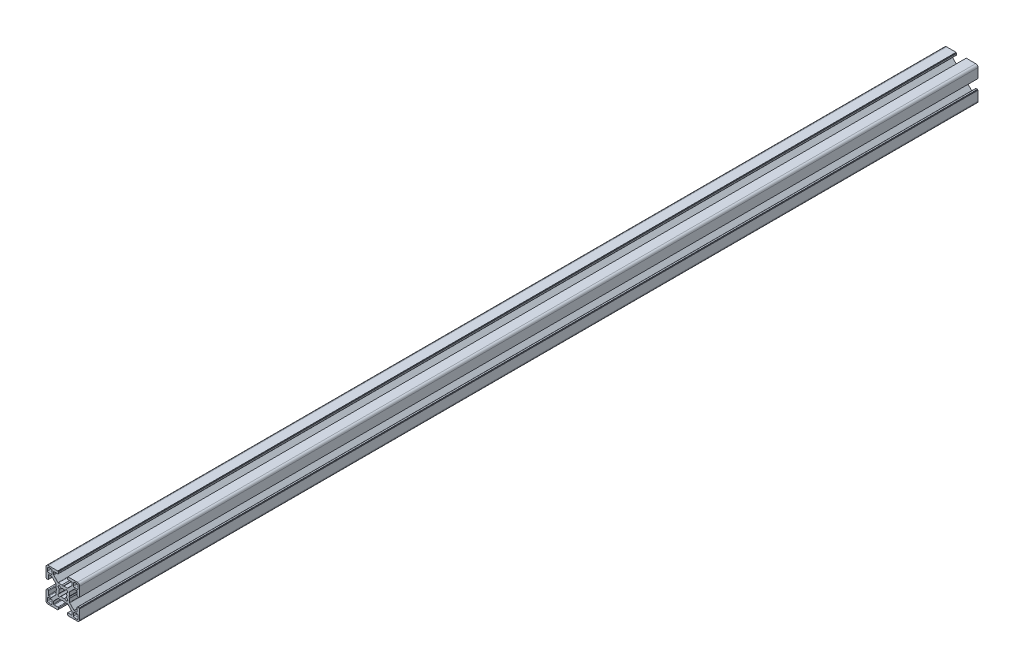
SolidWorks part; units mm, degrees
ref_plane "Front Plane" through (0, 0, 0) normal (0, 0, 1) x (1, 0, 0)
ref_plane "Top Plane" through (0, 0, 0) normal (0, 1, 0) x (1, 0, 0)
ref_plane "Right Plane" through (0, 0, 0) normal (1, 0, 0) x (0, 0, -1)
sketch "Sketch1" plane through (0, 0, 0) normal (0, 0, 1) x (1, 0, 0)
  line L0 (-15, 0) -> (15, 0) construction
  line L1 (0, -15) -> (0, 15) construction
  line L2 (-4.5, 15) -> (4.5, 15) construction
  line L3 (-4, -15) -> (4, -15) construction
  line L4 (-4.5, 15) -> (-4.5, 14.5)
  line L5 (-4.5, 14.5) -> (-4, 14.5)
  line L6 (-4, 14.5) -> (-4, 13.29)
  line L7 (-4.5, 12.79) -> (-7.7675, 12.79)
  line L8 (-8.2675, 12.29) -> (-8.2675, 10.2707)
  line L9 (-8.1211, 9.9171) -> (-4.3504, 6.1464)
  line L10 (-3.9968, 6) -> (0, 6)
  line L11 (0, 0) -> (-15, 15) construction
  line L12 (-4.5, 15) -> (-12.968, 15)
  line L14 (-12.705, 9.5135) -> (-10.5135, 9.5135)
  line L15 (-13.705, 10.5135) -> (-13.705, 12.705)
  line L16 (-12.705, 13.705) -> (-10.5135, 13.705)
  line L17 (-9.5135, 10.5135) -> (-9.5135, 12.705)
  line L18 (-13.705, 9.5135) -> (-9.5135, 13.705) construction
  line L19 (-13.705, 13.705) -> (-9.5135, 9.5135) construction
  line L20 (-3.1568, 4.5038) -> (-1.5303, 3.1477) construction
  line L21 (-4.5038, 3.1568) -> (-3.1477, 1.5303) construction
  line L22 (-6, 3.9968) -> (-6, 0)
  line L23 (-9.9171, 8.1211) -> (-6.1464, 4.3504)
  line L24 (-15, 4.5) -> (-15, 12.968)
  line L25 (-12.29, 8.2675) -> (-10.2707, 8.2675)
  line L26 (-12.79, 4.5) -> (-12.79, 7.7675)
  line L27 (-14.5, 4) -> (-13.29, 4)
  line L28 (-14.5, 4.5) -> (-14.5, 4)
  line L29 (-15, 4.5) -> (-14.5, 4.5)
  circle A0 centre (0, 0) radius 3.5
  arc A1 (-12.968, 15) -> (-15, 12.968) centre (-12.968, 12.968) ccw
  circle A2 centre (0, 0) radius 5.5 construction
  arc A3 (-10.5135, 9.5135) -> (-9.5135, 10.5135) centre (-10.5135, 10.5135) ccw
  arc A4 (-13.705, 12.705) -> (-12.705, 13.705) centre (-12.705, 12.705) cw
  arc A5 (-10.5135, 13.705) -> (-9.5135, 12.705) centre (-10.5135, 12.705) cw
  arc A6 (-12.705, 9.5135) -> (-13.705, 10.5135) centre (-12.705, 10.5135) cw
  arc A7 (-12.79, 4.5) -> (-13.29, 4) centre (-13.29, 4.5) cw
  arc A8 (-12.29, 8.2675) -> (-12.79, 7.7675) centre (-12.29, 7.7675) ccw
  arc A9 (-9.9171, 8.1211) -> (-10.2707, 8.2675) centre (-10.2707, 7.7675) ccw
  arc A10 (-6, 3.9968) -> (-6.1464, 4.3504) centre (-6.5, 3.9968) ccw
  arc A11 (-4.3504, 6.1464) -> (-3.9968, 6) centre (-3.9968, 6.5) ccw
  arc A12 (-4, 13.29) -> (-4.5, 12.79) centre (-4.5, 13.29) cw
  arc A13 (-7.7675, 12.79) -> (-8.2675, 12.29) centre (-7.7675, 12.29) ccw
  arc A14 (-8.2675, 10.2707) -> (-8.1211, 9.9171) centre (-7.7675, 10.2707) ccw
  point P4 (0, 0)
  point P8 (0, 0)
  point P13 (0, 15)
  point P15 (0, -15)
  point P16 (0, 6)
  point P23 (-11.6092, 11.6093)
  point P26 (0, 6)
  point P62 (-12.79, 4)
  point P65 (-12.79, 8.2675)
  point P68 (-10.0636, 8.2675)
  point P71 (-6, 4.2039)
  point P74 (-4.2039, 6)
  point P77 (-4, 12.79)
  point P80 (-8.2675, 12.79)
  point P83 (-8.2675, 10.0636)
  dimension "Center Hole Diameter" = 7
  dimension "D11" = 2.032
  dimension "D9" = 11
  dimension "D13" = 1
  dimension "D14" = 0.5
  dimension "Rail Height" = 30
  dimension "Rail Width" = 30
  dimension "T-Slot Width" = 8
  dimension "T-Slot Depth" = 9
  dimension "D1" = 9
  dimension "D2" = 45
  dimension "D3" = 8
  dimension "D4" = 2.21
  dimension "D5" = 16.535
  dimension "D7" = 2.54
  dimension "D6" = 1.295
  dimension "D8" = 1.246
  dimension "D10" = 10.36
  dimension "D12" = 1.905
sketch "Sketch2" plane through (0, 0, 0) normal (1, 0, 0) x (0, 0, -1)
  line L0 (-76.2, 0) -> (76.2, 0) construction
  line L2 (0, -15) -> (0, 15) construction
  line L3 (0, -15) -> (0, 15) construction
  line L4 (-76.2, -15) -> (-76.2, 15) construction
  line L5 (76.2, -15) -> (76.2, 15) construction
  point P0 (-38.7, 0)
  point P3 (0, 0)
  point P4 (38.7, 0)
  point P12 (-76.2, 0)
  point P14 (76.2, 0)
  dimension "Length" = 152.4
  dimension "D1" = 37.5
sketch "Sketch3" plane through (0, 0, 0) normal (0, 0, 1) x (1, 0, 0)
  line L0 (-4.5038, 3.1568) -> (-3.1477, 1.5303)
  line L1 (0, 3.5) -> (0, 5.5)
  line L2 (-5.5, 0) -> (-3.5, 0)
  line L7 (-6, 3.9968) -> (-6, 0) construction
  line L31 (-9.9171, 8.1211) -> (-6.1464, 4.3504) construction
  line L117 (-12.29, 8.2675) -> (-10.2707, 8.2675) construction
  line L118 (-12.79, 4.5) -> (-12.79, 7.7675) construction
  line L157 (-12.705, 9.5135) -> (-10.5135, 9.5135)
  line L158 (-9.5135, 10.5135) -> (-9.5135, 12.705)
  line L163 (-10.5135, 13.705) -> (-12.705, 13.705)
  line L164 (-13.705, 12.705) -> (-13.705, 10.5135)
  line L165 (-12.705, 9.5135) -> (-10.5135, 9.5135)
  line L166 (-9.5135, 10.5135) -> (-9.5135, 12.705)
  line L167 (-10.5135, 13.705) -> (-12.705, 13.705)
  line L168 (-13.705, 12.705) -> (-13.705, 10.5135)
  line L169 (-14.5, 4) -> (-13.29, 4) construction
  line L170 (-14.5, 4.5) -> (-14.5, 4) construction
  line L171 (-15, 4.5) -> (-14.5, 4.5) construction
  line L172 (-15, 4.5) -> (-15, 12.968) construction
  line L173 (-4.5, 15) -> (-12.968, 15) construction
  line L174 (-4.5, 15) -> (-4.5, 14.5) construction
  line L175 (-4.5, 14.5) -> (-4, 14.5) construction
  line L176 (-4, 14.5) -> (-4, 13.29) construction
  line L177 (-4.5, 12.79) -> (-7.7675, 12.79) construction
  line L178 (-8.2675, 12.29) -> (-8.2675, 10.2707) construction
  line L179 (-8.1211, 9.9171) -> (-4.3504, 6.1464) construction
  line L180 (-3.9968, 6) -> (0, 6) construction
  line L181 (-6, 3.9968) -> (-6, 0.866)
  line L182 (-9.9171, 8.1211) -> (-6.1464, 4.3504)
  line L183 (-12.29, 8.2675) -> (-10.2707, 8.2675)
  line L184 (-12.79, 4.5) -> (-12.79, 7.7675)
  line L185 (-14.5, 4) -> (-13.29, 4)
  line L186 (-14.5, 4.5) -> (-14.5, 4)
  line L187 (-15, 4.5) -> (-14.5, 4.5)
  line L188 (-15, 4.5) -> (-15, 12.968)
  line L189 (-4.5, 15) -> (-12.968, 15)
  line L190 (-4.5, 15) -> (-4.5, 14.5)
  line L191 (-4.5, 14.5) -> (-4, 14.5)
  line L192 (-4, 14.5) -> (-4, 13.29)
  line L193 (-4.5, 12.79) -> (-7.7675, 12.79)
  line L194 (-8.2675, 12.29) -> (-8.2675, 10.2707)
  line L195 (-8.1211, 9.9171) -> (-4.3504, 6.1464)
  line L196 (-3.9968, 6) -> (-0.866, 6)
  line L197 (-0.866, 6) -> (0, 5.5)
  line L198 (0, -15) -> (0, 15) construction
  line L199 (0, 0) -> (-15, 15) construction
  line L200 (0, 0) -> (-15, 15) construction
  line L201 (-3.1568, 4.5038) -> (-1.5303, 3.1477) construction
  line L202 (-3.1568, 4.5038) -> (-1.5303, 3.1477)
  line L203 (-6, 0.866) -> (-5.5, 0)
  line L204 (-15, 0) -> (15, 0) construction
  line L205 (-15, 0) -> (15, 0) construction
  line L206 (0, -15) -> (0, 15) construction
  arc A0 (-3.5, 0) -> (-3.1477, 1.5303) centre (0, 0) cw
  arc A10 (-6, 3.9968) -> (-6.1464, 4.3504) centre (-6.5, 3.9968) ccw construction
  circle A16 centre (0, 0) radius 3.5
  arc A18 (0, 3.5) -> (-1.5303, 3.1477) centre (0, 0) ccw
  arc A20 (-9.9171, 8.1211) -> (-10.2707, 8.2675) centre (-10.2707, 7.7675) ccw construction
  arc A22 (-12.29, 8.2675) -> (-12.79, 7.7675) centre (-12.29, 7.7675) ccw construction
  arc A28 (-13.29, 4) -> (-12.79, 4.5) centre (-13.29, 4.5) ccw construction
  arc A29 (-10.5135, 9.5135) -> (-9.5135, 10.5135) centre (-10.5135, 10.5135) ccw
  arc A30 (-9.5135, 12.705) -> (-10.5135, 13.705) centre (-10.5135, 12.705) ccw
  arc A31 (-12.705, 13.705) -> (-13.705, 12.705) centre (-12.705, 12.705) ccw
  arc A32 (-13.705, 10.5135) -> (-12.705, 9.5135) centre (-12.705, 10.5135) ccw
  arc A33 (-10.5135, 9.5135) -> (-9.5135, 10.5135) centre (-10.5135, 10.5135) ccw
  arc A34 (-9.5135, 12.705) -> (-10.5135, 13.705) centre (-10.5135, 12.705) ccw
  arc A35 (-12.705, 13.705) -> (-13.705, 12.705) centre (-12.705, 12.705) ccw
  arc A36 (-13.705, 10.5135) -> (-12.705, 9.5135) centre (-12.705, 10.5135) ccw
  arc A37 (-12.968, 15) -> (-15, 12.968) centre (-12.968, 12.968) ccw construction
  arc A38 (-4.5, 12.79) -> (-4, 13.29) centre (-4.5, 13.29) ccw construction
  arc A39 (-7.7675, 12.79) -> (-8.2675, 12.29) centre (-7.7675, 12.29) ccw construction
  arc A40 (-8.2675, 10.2707) -> (-8.1211, 9.9171) centre (-7.7675, 10.2707) ccw construction
  arc A41 (-4.3504, 6.1464) -> (-3.9968, 6) centre (-3.9968, 6.5) ccw construction
  arc A42 (-6, 3.9968) -> (-6.1464, 4.3504) centre (-6.5, 3.9968) ccw
  arc A43 (-9.9171, 8.1211) -> (-10.2707, 8.2675) centre (-10.2707, 7.7675) ccw
  arc A44 (-12.29, 8.2675) -> (-12.79, 7.7675) centre (-12.29, 7.7675) ccw
  arc A45 (-13.29, 4) -> (-12.79, 4.5) centre (-13.29, 4.5) ccw
  arc A46 (-12.968, 15) -> (-15, 12.968) centre (-12.968, 12.968) ccw
  arc A47 (-4.5, 12.79) -> (-4, 13.29) centre (-4.5, 13.29) ccw
  arc A48 (-7.7675, 12.79) -> (-8.2675, 12.29) centre (-7.7675, 12.29) ccw
  arc A49 (-8.2675, 10.2707) -> (-8.1211, 9.9171) centre (-7.7675, 10.2707) ccw
  arc A50 (-4.3504, 6.1464) -> (-3.9968, 6) centre (-3.9968, 6.5) ccw
  circle A51 centre (0, 0) radius 5.5 construction
  arc A52 (-3.1568, 4.5038) -> (-4.5038, 3.1568) centre (0, 0) ccw
  dimension "D3" = 60
  dimension "D4" = 60
  dimension "D1" = 0
  dimension "D2" = 0
extrude "Boss-Extrude1" add sketch "Sketch3" along normal mid plane 800
pattern_circular "CirPattern1" count 4 over 360 about axis through (0, 0, 76.2) along (0, 0, -1) of "Boss-Extrude1"
ref_plane "Contact Plane1" through (15, 0, 0) normal (1, 0, 0) x (0, 0, -1)
ref_plane "Contact Plane2" through (0, -15, 0) normal (0, 1, 0) x (1, 0, 0)
ref_plane "Contact Plane3" through (-15, 0, 0) normal (1, 0, 0) x (0, 0, -1)
ref_plane "Contact Plane4" through (0, 15, 0) normal (0, 1, 0) x (1, 0, 0)
equation "\"D1@Sketch2\" = \"Rail Height@Sketch1\" * 1.25"
equation "\"D1@Sketch1\"=\"T-Slot Width@Sketch1\"+1mm"
equation "\"D3@Sketch1\"=\"T-Slot Width@Sketch1\""
equation "\"D1@Boss-Extrude1\"=\"Length\""
equation "\"Length\" = 800mm"
